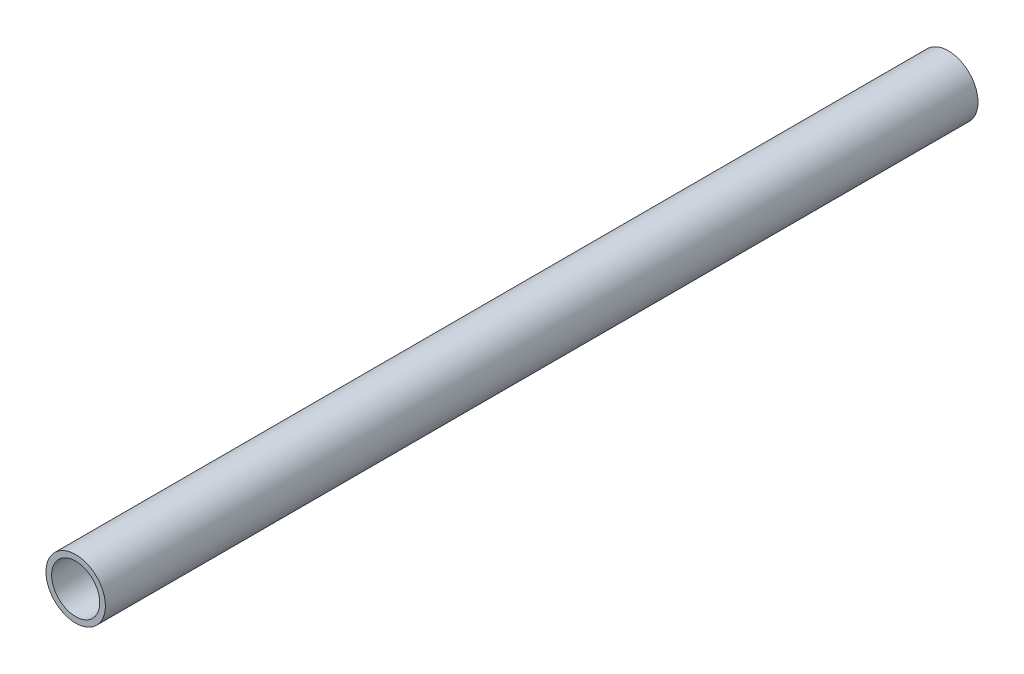
SolidWorks part; units mm, degrees
material "AISI 4130 Steel, annealed at 865C"
ref_plane "Front Plane" through (0, 0, 0) normal (0, 0, 1) x (1, 0, 0)
ref_plane "Top Plane" through (0, 0, 0) normal (0, 1, 0) x (1, 0, 0)
ref_plane "Right Plane" through (0, 0, 0) normal (1, 0, 0) x (0, 0, -1)
sketch "Sketch1" plane through (0, 0, 0) normal (0, 0, 1) x (1, 0, 0)
  circle A0 centre (0, 0) radius 6.477
  circle A1 centre (0, 0) radius 8.001
  dimension "D1" = 12.954
  dimension "D2" = 16.002
extrude "Boss-Extrude1" add sketch "Sketch1" along normal blind 234.95
sketch "Sketch2" plane through (0, 0, 0) normal (1, 0, 0) x (0, 0, -1)
  line L0 (0, 3.175) -> (-31.75, 3.175)
  line L1 (0, 55) -> (0, -55) construction
  line L2 (-31.75, -3.175) -> (0, -3.175)
  line L3 (-33.274, 1.651) -> (-33.274, -1.651)
  line L4 (0, -8.001) -> (0, 8.001) construction
  arc A0 (-33.274, 1.651) -> (-31.75, 3.175) centre (-31.75, 1.651) cw
  arc A1 (-31.75, -3.175) -> (-33.274, -1.651) centre (-31.75, -1.651) cw
  dimension "D5" = 31.75
  dimension "D6" = 33.274
  dimension "D1" = 33.274
  dimension "D2" = 31.75
  dimension "D3" = 6.35
  dimension "D4" = 3.175
